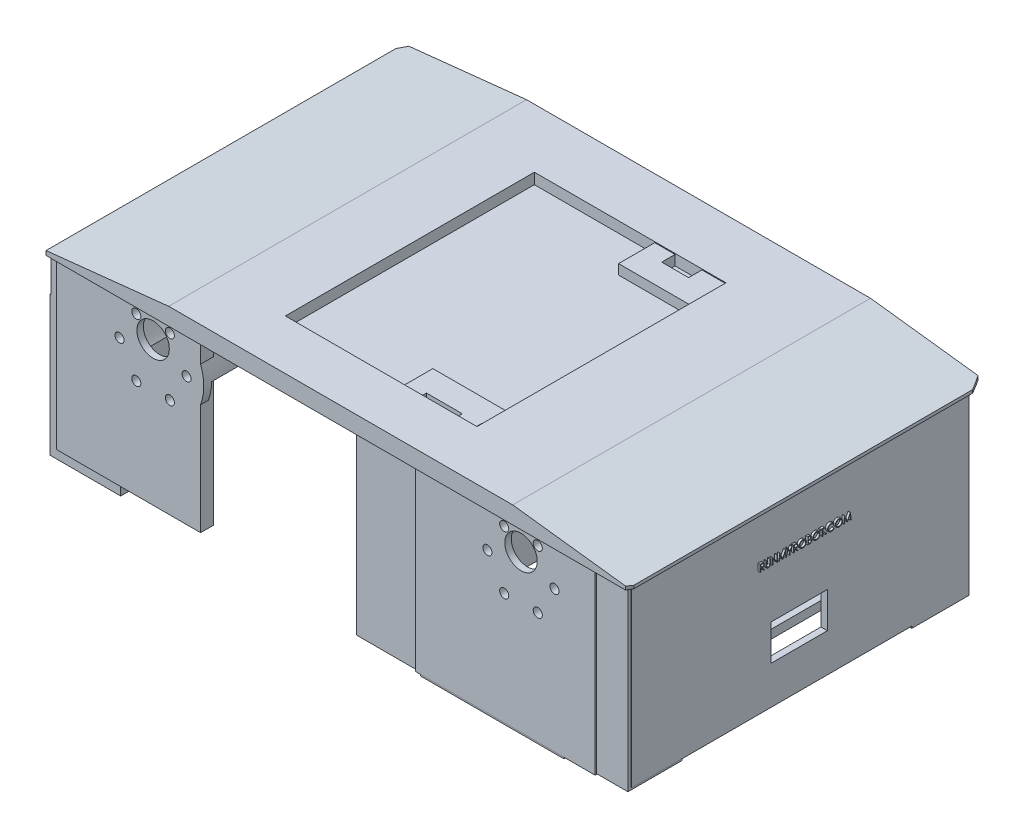
SolidWorks part; units mm, degrees
ref_plane "Front Plane" through (0, 0, 0) normal (0, 0, 1) x (1, 0, 0)
ref_plane "Top Plane" through (0, 0, 0) normal (0, 1, 0) x (1, 0, 0)
ref_plane "Right Plane" through (0, 0, 0) normal (1, 0, 0) x (0, 0, -1)
sketch "MotorHoldersSketch" plane through (0, 0, 0) normal (0, 0, 1) x (1, 0, 0)
  line L0 (0, 0) -> (170, 0) construction
  line L1 (0, 0) -> (0, 23.41) construction
  line L2 (170, 0) -> (170, 23.41) construction
  circle A0 centre (0, 0) radius 23.41
  circle A1 centre (170, 0) radius 23.41
ref_axis "MotorCenterAxis1" through (0, 0, 0) along (0, 0, 1)
ref_axis "MotorCenterAxis2" through (170, 0, 0) along (0, 0, 1)
extrude "MotorHolders" add sketch "MotorHoldersSketch" along normal blind 80 and the other way blind 80
sketch "Sketch3" plane through (0, 0, 0) normal (0, 0, 1) x (1, 0, 0)
  line L1 (1.9406, 21.133) -> (168.3435, 21.133)
  line L2 (1.9406, 21.133) -> (1.9406, 18.3155)
  line L3 (1.9406, 18.3155) -> (168.3435, 18.3155)
  line L4 (168.3435, 21.133) -> (168.3435, 18.3155)
sketch "Sketch4" plane through (0, 0, 0) normal (0, 1, 0) x (1, 0, 0)
  line L1 (221.2811, -76.3794) -> (-41.4939, -76.3794)
  line L2 (221.2811, -76.3794) -> (221.2811, 76.7331)
  line L3 (221.2811, 76.7331) -> (-41.4939, 76.7331)
  line L4 (-41.4939, -76.3794) -> (-41.4939, 76.7331)
extrude "Cut-Extrude1" cut sketch "Sketch4" against normal blind 26
ref_axis "Axis3" through (170, 0, 0) along (0, -1, 0)
sketch3d "ReferencePlanePosition"
  line L0 (170, 0, 0) -> (170, -34.8293, 0)
  line L1 (170, 0, 0) -> (170, -38.994, 0) construction
ref_plane "ReferencePlane" through (170, -34.8293, 0) normal (0, -1, 0) x (-1, 0, 0)
sketch "Sketch6" plane through (170, -34.8293, 0) normal (0, -1, 0) x (-1, 0, 0)
  line L1 (219.5858, 78.949) -> (145.1716, 78.949)
  line L2 (219.5858, 78.949) -> (219.5858, 65.5282)
  line L3 (219.5858, 65.5282) -> (145.1716, 65.5282)
  line L4 (145.1716, 78.949) -> (145.1716, 65.5282)
  line L5 (219.3147, -52.1095) -> (186.667, -52.1095)
  line L6 (219.3147, -52.1095) -> (219.3147, -78.2822)
  line L7 (219.3147, -78.2822) -> (186.667, -78.2822)
  line L8 (186.667, -52.1095) -> (186.667, -78.2822)
  line L9 (75.6651, 77.8627) -> (19.9904, 77.8627)
  line L10 (75.6651, 77.8627) -> (75.6651, 40.7512)
  line L11 (75.6651, 40.7512) -> (19.9904, 40.7512)
  line L12 (19.9904, 77.8627) -> (19.9904, 40.7512)
  line L13 (76.5596, -44.1716) -> (20.0852, -44.1716)
  line L14 (76.5596, -44.1716) -> (76.5596, -79.4437)
  line L15 (76.5596, -79.4437) -> (20.0852, -79.4437)
  line L16 (20.0852, -44.1716) -> (20.0852, -79.4437)
  line L17 (213.765, 73.0364) -> (192.9548, 73.0364)
  line L18 (213.765, 73.0364) -> (213.765, 71.0153)
  line L19 (213.765, 71.0153) -> (192.9548, 71.0153)
  line L20 (192.9548, 73.0364) -> (192.9548, 71.0153)
  line L21 (41.3552, 69.1777) -> (28.5109, 69.1777)
  line L22 (41.3552, 69.1777) -> (41.3552, 50.8413)
  line L23 (41.3552, 50.8413) -> (28.5109, 50.8413)
  line L24 (28.5109, 69.1777) -> (28.5109, 50.8413)
  line L25 (43.3068, -72.8101) -> (32.1723, -72.8101)
  line L26 (43.3068, -72.8101) -> (43.3068, -54.7747)
  line L27 (43.3068, -54.7747) -> (32.1723, -54.7747)
  line L28 (32.1723, -72.8101) -> (32.1723, -54.7747)
  line L29 (211.9411, -70.4881) -> (201.0982, -70.4881)
  line L30 (211.9411, -70.4881) -> (211.9411, -60.1404)
  line L31 (211.9411, -60.1404) -> (201.0982, -60.1404)
  line L32 (201.0982, -70.4881) -> (201.0982, -60.1404)
  line L37 (66.2772, 51.3198) -> (53.8697, 51.3198)
  line L38 (66.2772, 51.3198) -> (66.2772, 67.7632)
  line L39 (66.2772, 67.7632) -> (53.8697, 67.7632)
  line L40 (53.8697, 51.3198) -> (53.8697, 67.7632)
  line L45 (68.2481, -69.8638) -> (51.7107, -69.8638)
  line L46 (68.2481, -69.8638) -> (68.2481, -55.4273)
  line L47 (68.2481, -55.4273) -> (51.7107, -55.4273)
  line L48 (51.7107, -69.8638) -> (51.7107, -55.4273)
  line L49 (-20.7001, -79.4437) -> (-48.8506, -79.4437)
  line L50 (-20.7001, -79.4437) -> (-20.7001, -54.5097)
  line L51 (-20.7001, -54.5097) -> (-48.8506, -54.5097)
  line L52 (-48.8506, -79.4437) -> (-48.8506, -54.5097)
  line L53 (-18.3873, 77.8627) -> (-49.0581, 77.8627)
  line L54 (-18.3873, 77.8627) -> (-18.3873, 51.5325)
  line L55 (-18.3873, 51.5325) -> (-49.0581, 51.5325)
  line L56 (-49.0581, 77.8627) -> (-49.0581, 51.5325)
  line L57 (-41.8141, -72.8101) -> (-31.6362, -72.8101)
  line L58 (-41.8141, -72.8101) -> (-41.8141, -62.9794)
  line L59 (-41.8141, -62.9794) -> (-31.6362, -62.9794)
  line L60 (-31.6362, -72.8101) -> (-31.6362, -62.9794)
  line L61 (-31.6362, 69.1777) -> (-41.5347, 69.1777)
  line L62 (-31.6362, 69.1777) -> (-31.6362, 58.5421)
  line L63 (-31.6362, 58.5421) -> (-41.5347, 58.5421)
  line L64 (-41.5347, 69.1777) -> (-41.5347, 58.5421)
extrude "PowerBankHolders" add sketch "Sketch6" along normal blind 30 and the other way blind 59 separate body
sketch3d "3DSketch3"
  line L0 (170, 0, 0) -> (170, -64.5, 0) construction
ref_plane "Plane2" through (170, -64.5, 0) normal (0, -1, 0) x (-1, 0, 0)
sketch "Sketch7" plane through (170, -64.5, 0) normal (0, -1, 0) x (-1, 0, 0)
  line L1 (-9.5047, -80.801) -> (181.32, -80.801)
  line L2 (-9.5047, -80.801) -> (-9.5047, 73.8662)
  line L3 (-9.5047, 73.8662) -> (181.32, 73.8662)
  line L4 (181.32, -80.801) -> (181.32, 73.8662)
  line L5 (151.8712, -54.3972) -> (26.5361, -54.3972)
  line L6 (151.8712, -54.3972) -> (151.8712, 46.2413)
  line L7 (151.8712, 46.2413) -> (26.5361, 46.2413)
  line L8 (26.5361, -54.3972) -> (26.5361, 46.2413)
ref_point "Point1"
ref_point "Point2"
sketch3d "3DSketch11"
  line L0 (0, 0, -80) -> (170, 0, 80) construction
  point P4 (85, 0, 0)
sketch "MotorHolderExtrudeSketch" plane through (0, 0, 0) normal (0, 0, 1) x (1, 0, 0)
  circle A0 centre (170, 0) radius 20.415
  circle A1 centre (0, 0) radius 20.415
  circle A3 centre (0, 0) radius 23.41 construction
  circle A4 centre (170, 0) radius 23.41 construction
ref_point "TopOfMotors"
ref_plane "TangentToTopOfMotors" through (0, -20.415, 0) normal (0, 1, 0) x (1, 0, 0)
ref_axis "Axis4" through (85, 0, 0) along (0, -1, 0)
ref_plane "BottomOfPowerBankRegion" through (0, -20.425, 0) normal (0, 1, 0) x (1, 0, 0)
sketch "Sketch11" plane through (0, -20.425, 0) normal (0, 1, 0) x (1, 0, 0)
  line L0 (-18.9327, 3.7419) -> (188.9327, -3.7419) construction
  line L5 (-18.9327, -64.7581) -> (-18.9327, 72.2419)
  line L6 (188.9327, 63.7581) -> (188.9327, -71.2419)
  line L7 (188.9327, -71.2419) -> (-18.9327, -64.7581)
  line L8 (188.9327, 63.7581) -> (-18.9327, 72.2419)
  circle A0 centre (85, 0) radius 104 construction
ref_point "CenterAtBottomOfPowerBank"
ref_plane "TopOfPowerBankPlane" through (0, -54.425, 0) normal (0, 1, 0) x (1, 0, 0)
sketch "Sketch13" plane through (0, -54.425, 0) normal (0, 1, 0) x (1, 0, 0)
  line L1 (-19.4498, 72.5454) -> (166.1636, 72.5454)
  line L2 (-19.4498, 72.5454) -> (-19.4498, -78.2051)
  line L3 (-19.4498, -78.2051) -> (166.1636, -78.2051)
  line L4 (166.1636, 72.5454) -> (166.1636, -78.2051)
  line L5 (19.3173, -49.583) -> (137.9607, -49.583)
  line L6 (19.3173, -49.583) -> (19.3173, -21.0549)
  line L7 (19.3173, -21.0549) -> (137.9607, -21.0549)
  line L8 (137.9607, -49.583) -> (137.9607, -21.0549)
  line L9 (19.3173, 56.6778) -> (137.9607, 56.6778)
  line L10 (19.3173, 56.6778) -> (19.3173, 36.3234)
  line L11 (19.3173, 36.3234) -> (137.9607, 36.3234)
  line L12 (137.9607, 56.6778) -> (137.9607, 36.3234)
  line L13 (19.3173, 18.3186) -> (137.9607, 18.3186)
  line L14 (19.3173, 18.3186) -> (19.3173, -7.3615)
  line L15 (19.3173, -7.3615) -> (137.9607, -7.3615)
  line L16 (137.9607, 18.3186) -> (137.9607, -7.3615)
sketch "Sketch15" plane through (150.0096, 0, 0) normal (1, 0, 0) x (0, 0, -1)
  line L1 (72.5313, -25.7765) -> (45.7099, -25.7765)
  line L2 (72.5313, -25.7765) -> (72.5313, -24.2242)
  line L3 (72.5313, -24.2242) -> (45.7099, -24.2242)
  line L4 (45.7099, -25.7765) -> (45.7099, -24.2242)
extrude "PowerBankCut" cut sketch "Sketch11" against normal blind 64
ref_plane "Plane6" through (0, 0, 0) normal (0, 0, 1) x (1, 0, 0)
sketch "MotorGeometry1" plane through (0, 0, 0) normal (0, 0, 1) x (1, 0, 0)
  line L0 (170, 0) -> (170, -13.42)
  line L1 (170, 0) -> (170, -34.8293) construction
  line L2 (170, -13.42) -> (162.25, -13.42) construction
  line L3 (170, -13.42) -> (177.75, -13.42) construction
  line L4 (170, -13.42) -> (170, 7) construction
  line L5 (170, 0) -> (185.5, 0) construction
  line L6 (170, 0) -> (154.5, 0) construction
  line L7 (170, 0) -> (170, 13.42) construction
  line L8 (170, 0) -> (170, 23.41) construction
  line L9 (170, 13.42) -> (177.75, 13.42) construction
  line L10 (170, 13.42) -> (162.25, 13.42)
ref_axis "BoltAxisA" through (185.5, 0, 0) along (0, 0, 1)
ref_axis "BoltAxisB" through (177.75, -13.42, 0) along (0, 0, 1)
ref_axis "BoltAxisC" through (162.25, -13.42, 0) along (0, 0, 1)
ref_axis "BoltAxisD" through (154.5, 0, 0) along (0, 0, 1)
ref_axis "BoltAxisE" through (162.25, 13.42, 0) along (0, 0, 1)
ref_axis "BoltAxisF" through (177.75, 13.42, 0) along (0, 0, 1)
ref_point "Point6"
ref_point "Point7"
ref_point "Point8"
ref_point "Point9"
ref_point "Point10"
ref_point "Point11"
ref_point "Point12"
ref_point "Point13"
ref_point "Point14"
ref_point "Point15"
ref_point "Point16"
ref_point "Point17"
ref_plane "Plane7" through (0, 0, 0) normal (0, 0, 1) x (1, 0, 0)
sketch "MotorGeometry2" plane through (0, 0, 0) normal (0, 0, 1) x (1, 0, 0)
  line L0 (0, 0) -> (0, -13.42) construction
  line L1 (0, -13.42) -> (7.75, -13.42) construction
  line L2 (0, -13.42) -> (-7.75, -13.42) construction
  line L3 (0, 0) -> (0, 13.42)
  line L4 (0, -13.42) -> (0, 7) construction
  line L5 (0, 13.42) -> (7.75, 13.42) construction
  line L6 (0, 13.42) -> (-7.75, 13.42) construction
  line L7 (0, 0) -> (15.5, 0) construction
  line L8 (0, 0) -> (-15.5, 0) construction
  line L9 (0, 0) -> (0, 23.41) construction
ref_axis "Axis11" through (15.5, 0, 0) along (0, 0, 1)
ref_axis "Axis12" through (7.75, 13.42, 0) along (0, 0, 1)
ref_axis "Axis13" through (-7.75, 13.42, 0) along (0, 0, 1)
ref_axis "Axis14" through (-15.5, 0, 0) along (0, 0, 1)
ref_axis "Axis15" through (-7.75, -13.42, 0) along (0, 0, 1)
ref_axis "Axis16" through (7.75, -13.42, 0) along (0, 0, 1)
ref_point "Point18"
ref_point "Point19"
ref_point "Point20"
ref_point "Point21"
ref_point "Point22"
ref_point "Point23"
ref_point "Point24"
ref_point "Point25"
ref_point "Point26"
ref_point "Point27"
ref_point "Point28"
ref_point "Point29"
ref_plane "BottomPlane" through (0, 19.575, 0) normal (0, 1, 0) x (1, 0, 0)
ref_axis "OutputShaftReference1" through (0, 7, 0) along (0, 0, 1)
ref_point "Point35"
ref_axis "OutputShaftReference2" through (170, 7, 0) along (0, 0, 1)
sketch "Sketch21" plane through (0, 19.575, 0) normal (0, 1, 0) x (1, 0, 0)
  line L0 (219.6842, -79.5488) -> (-50.341, -79.5488) construction
  line L1 (-50.341, -79.5488) -> (-50.341, 79.7899) construction
  line L2 (-50.341, 79.7899) -> (219.6842, 79.7899) construction
  line L3 (219.6842, 79.7899) -> (219.6842, -79.5488) construction
  line L4 (127.2472, -57.5918) -> (127.2472, 57.4773)
  line L5 (127.2472, 57.4773) -> (38.7099, 57.4773)
  line L6 (38.7099, 57.4773) -> (38.7099, -57.5918)
  line L7 (38.7099, -57.5918) -> (127.2472, -57.5918)
  circle A0 centre (85, 0) radius 156.3953
extrude "BottomPlate" add sketch "Sketch21" along normal blind 5 and the other way blind 3
ref_plane "HoleReferencePlane1" through (0, 0, 80) normal (0, 0, 1) x (1, 0, 0)
ref_point "OutputShaftPosition3"
ref_point "OutputShaftPosition1"
sketch "Sketch23" plane through (0, 0, 80) normal (0, 0, 1) x (1, 0, 0)
  line L1 (21.9586, -59.3229) -> (-44.5901, -59.3229)
  line L2 (21.9586, -59.3229) -> (21.9586, 21.8402)
  line L3 (21.9586, 21.8402) -> (-44.5901, 21.8402)
  line L4 (-44.5901, -59.3229) -> (-44.5901, 21.8402)
  line L5 (121.3218, 21.8402) -> (204.258, 21.8402)
  line L6 (121.3218, 21.8402) -> (121.3218, -65.2231)
  line L7 (121.3218, -65.2231) -> (204.258, -65.2231)
  line L8 (204.258, 21.8402) -> (204.258, -65.2231)
extrude "MotorMountingSupport1" add sketch "Sketch23" against normal blind 6
ref_plane "HoleReferencePlane2" through (0, 0, -80) normal (0, 0, -1) x (-1, 0, 0)
ref_point "OutputShaftPosition4"
ref_point "OutputShaftPosition2"
sketch "Sketch24" plane through (0, 0, -80) normal (0, 0, -1) x (-1, 0, 0)
  line L1 (-202.1905, -67.1257) -> (-139.5471, -67.1257)
  line L2 (-202.1905, -67.1257) -> (-202.1905, 19.2374)
  line L3 (-202.1905, 19.2374) -> (-139.5471, 19.2374)
  line L4 (-139.5471, -67.1257) -> (-139.5471, 19.2374)
  line L5 (-24.3642, -64.1521) -> (29.5505, -64.1521)
  line L6 (-24.3642, -64.1521) -> (-24.3642, 22.5226)
  line L7 (-24.3642, 22.5226) -> (29.5505, 22.5226)
  line L8 (29.5505, -64.1521) -> (29.5505, 22.5226)
extrude "MotorMountingSuppor2" add sketch "Sketch24" against normal blind 6
sketch "Sketch17" plane through (0, 0, 80) normal (0, 0, 1) x (1, 0, 0)
  circle A0 centre (185.5, 0) radius 2.1
  circle A1 centre (177.75, -13.42) radius 2.1
  circle A2 centre (162.25, -13.42) radius 2.1
  circle A3 centre (154.5, 0) radius 2.1
  circle A4 centre (162.25, 13.42) radius 2.1
  circle A5 centre (177.75, 13.42) radius 2.1
  circle A6 centre (170, 7) radius 7.5
extrude "MotorHoles1" cut sketch "Sketch17" against normal blind 31.5
sketch "Sketch19" plane through (0, 0, -80) normal (0, 0, -1) x (-1, 0, 0)
  circle A0 centre (-185.5, 0) radius 2.1
  circle A1 centre (-177.75, -13.42) radius 2.1
  circle A2 centre (-162.25, -13.42) radius 2.1
  circle A3 centre (-154.5, 0) radius 2.1
  circle A4 centre (-162.25, 13.42) radius 2.1
  circle A5 centre (-177.75, 13.42) radius 2.1
  circle A6 centre (-170, 7) radius 7.5
sketch "BoltHolesSketch3" plane through (0, 0, 80) normal (0, 0, 1) x (1, 0, 0)
  circle A0 centre (7.75, -13.42) radius 2.1
  circle A1 centre (15.5, 0) radius 2.1
  circle A2 centre (7.75, 13.42) radius 2.1
  circle A3 centre (-7.75, 13.42) radius 2.1
  circle A4 centre (-15.5, 0) radius 2.1
  circle A5 centre (-7.75, -13.42) radius 2.1
  circle A6 centre (0, 7) radius 7.5
extrude "Cut-Extrude4" cut sketch "Sketch19" against normal blind 30
extrude "MotorHoles3" cut sketch "BoltHolesSketch3" against normal blind 31.5
sketch "BoltHolesSketch4" plane through (0, 0, -80) normal (0, 0, -1) x (-1, 0, 0)
  circle A0 centre (-15.5, 0) radius 2.1
  circle A1 centre (-7.75, 13.42) radius 2.1
  circle A2 centre (7.75, 13.42) radius 2.1
  circle A3 centre (15.5, 0) radius 2.1
  circle A4 centre (7.75, -13.42) radius 2.1
  circle A5 centre (-7.75, -13.42) radius 2.1
  circle A6 centre (0, 7) radius 7.5
extrude "MotorHoles4" cut sketch "BoltHolesSketch4" against normal blind 15
ref_plane "Front" through (219.0581, 0, 0) normal (1, 0, 0) x (0, 0, -1)
sketch "Sketch29" plane through (219.0581, 0, 0) normal (1, 0, 0) x (0, 0, -1)
  line L1 (76.6955, -63.9254) -> (-77.9397, -63.9254)
  line L2 (76.6955, -63.9254) -> (76.6955, 20.2062)
  line L3 (76.6955, 20.2062) -> (-77.9397, 20.2062)
  line L4 (-77.9397, -63.9254) -> (-77.9397, 20.2062)
  line L5 (-13.4507, -46.2559) -> (12.5493, -46.2559)
  line L6 (-13.4507, -46.2559) -> (-13.4507, -29.7559)
  line L7 (-13.4507, -29.7559) -> (12.5493, -29.7559)
  line L8 (12.5493, -46.2559) -> (12.5493, -29.7559)
extrude "Boss-Extrude8" add sketch "Sketch29" against normal blind 3
ref_plane "RaspberryPiBasePlane" through (0, 16.575, 0) normal (0, -1, 0) x (-1, 0, 0)
sketch "Sketch27" plane through (0, 16.575, 0) normal (0, -1, 0) x (-1, 0, 0)
  line L1 (31.6337, 64.5517) -> (-194.8264, 64.5517)
  line L2 (31.6337, 64.5517) -> (31.6337, -65.4335)
  line L3 (31.6337, -65.4335) -> (-194.8264, -65.4335)
  line L4 (-194.8264, 64.5517) -> (-194.8264, -65.4335)
extrude "Boss-Extrude6" add sketch "Sketch27" against normal blind 3
ref_plane "Plane12" through (0, -64.8293, 0) normal (0, -1, 0) x (-1, 0, 0)
sketch "Sketch28" plane through (0, -64.8293, 0) normal (0, -1, 0) x (-1, 0, 0)
  line L1 (-189.3897, -79.549) -> (-123.0026, -79.549)
  line L2 (-189.3897, -79.549) -> (-189.3897, 78.1499)
  line L3 (-189.3897, 78.1499) -> (-123.0026, 78.1499)
  line L4 (-123.0026, -79.549) -> (-123.0026, 78.1499)
extrude "Boss-Extrude7" add sketch "Sketch28" along normal blind 1.5 and the other way blind 2.5
extrude "MotorHolderCut" cut sketch "MotorHolderExtrudeSketch" against normal blind 77 and the other way blind 77
sketch "Sketch31" plane through (219.0581, 0, 0) normal (1, 0, 0) x (0, 0, -1)
  text T0 "RUNMYROBOT.COM"
extrude "Boss-Extrude9" add sketch "Sketch31" along normal blind 1
sketch "Sketch32" plane through (0, 19.575, 0) normal (0, 1, 0) x (1, 0, 0)
  line L1 (-48.8137, 84.6887) -> (220.392, 84.6887)
  line L2 (-48.8137, 84.6887) -> (-48.8137, -80.6635)
  line L3 (-48.8137, -80.6635) -> (220.392, -80.6635)
  line L4 (220.392, 84.6887) -> (220.392, -80.6635)
  line L5 (283.5566, -218.7268) -> (-136.4889, -218.7268)
  line L8 (-136.4889, -218.7268) -> (-136.4889, 206.3198)
  line L10 (283.5566, 206.3198) -> (283.5566, -218.7268)
  line L13 (283.5566, 206.3198) -> (-136.4889, 206.3198)
extrude "Cut-Extrude5" cut sketch "Sketch32" along normal blind 20 and the other way blind 20
sketch "Sketch35" plane through (0, 0, -84.6887) normal (0, 0, -1) x (-1, 0, 0)
  line L0 (69.0502, 16.3777) -> (-36.4474, 27.6206)
  line L1 (-36.4474, 27.6206) -> (71.6404, 26.1593)
  line L2 (69.0502, 16.3777) -> (71.6404, 26.1593)
  line L3 (-223.8844, 30.8145) -> (-223.8844, 17.5678)
  line L4 (-223.8844, 17.5678) -> (-116.0163, 30.8145)
  line L5 (-116.0163, 30.8145) -> (-223.8844, 30.8145)
  point P4 (-223.8844, 17.5678)
  point P7 (-36.4474, 27.6206)
  point P8 (-119.7455, 27.6206)
  point P9 (-116.0163, 30.8145)
extrude "Cut-Extrude7" cut sketch "Sketch35" against normal blind 200
